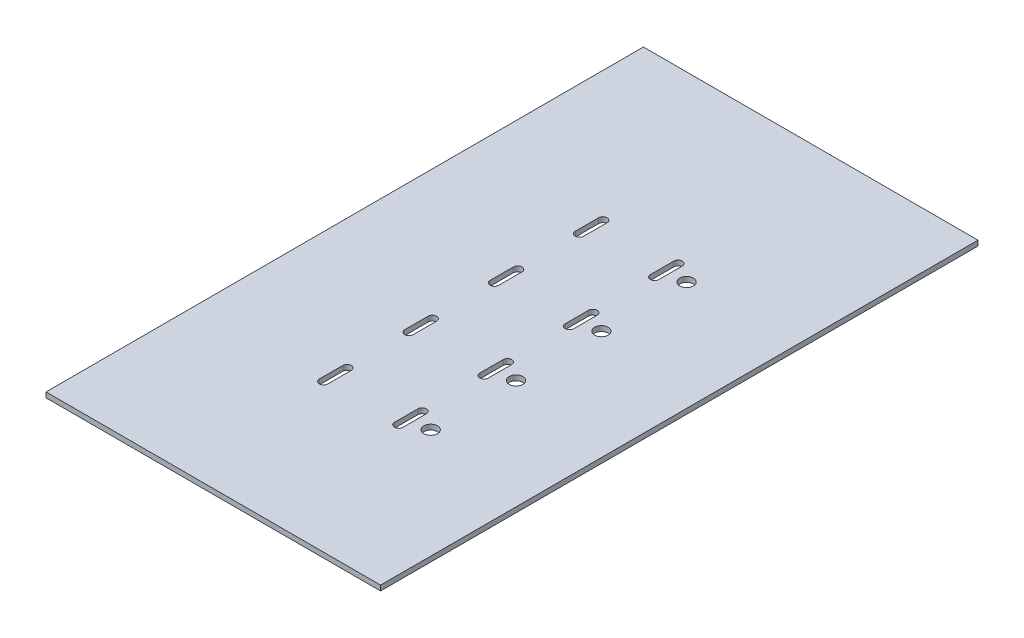
SolidWorks part; units mm, degrees
ref_plane "Front Plane" through (0, 0, 0) normal (0, 0, 1) x (1, 0, 0)
ref_plane "Top Plane" through (0, 0, 0) normal (0, 1, 0) x (1, 0, 0)
ref_plane "Right Plane" through (0, 0, 0) normal (1, 0, 0) x (0, 0, -1)
sketch "Sketch1" plane through (0, 0, 0) normal (0, 1, 0) x (1, 0, 0)
  line L1 (0, 0) -> (196, 0)
  line L2 (0, 0) -> (0, 350)
  line L3 (0, 350) -> (196, 350)
  line L4 (196, 0) -> (196, 350)
  dimension "D1" = 350
  dimension "D2" = 196
extrude "Boss-Extrude1" add sketch "Sketch1" along normal blind 3
hole_wizard "Ø8.0mm Dowel Hole1" positions "Sketch2" profile "Sketch3" hole size "Ø8.0" standard "AS" end condition up to next
sketch "Sketch2" plane through (0, 0, 0) normal (0, -1, 0) x (-1, 0, 0)
  point P0 (-131.875, 93.5)
  point P3 (-131.875, 143.5)
  point P6 (-131.875, 193.5067)
  point P9 (-131.875, 243.4059)
  point P13 (0, 0)
  point P14 (0, 0)
  point P15 (0, 0)
  point P16 (0, 0)
sketch "Sketch3" plane through (131.875, 0, -93.5) normal (1, 0, 0) x (0, 0, -1)
  line L0 (0, 0) -> (0, 3)
  line L1 (0, 3) -> (4, 3)
  line L2 (4, 3) -> (4, 0)
  line L5 (4, 0) -> (0, 0)
  line L11 (0, -6.35) -> (0, 107.95) construction
  dimension "Thru Hole Dia." = 8
  dimension "Thru Hole Depth" = 3
hole_wizard "Ø5.0mm Dowel Slot1" positions "Sketch4" profile "Sketch5" size "Ø5.0" standard "AS" slot yes end condition up to next
sketch "Sketch4" plane through (0, 0, 0) normal (0, -1, 0) x (-1, 0, 0)
  line L0 (-120, 84.15) -> (-120, 102.85) construction
  point P0 (-120, 93.5)
  point P7 (-76, 93.5)
  point P10 (-120, 143.5)
  point P13 (-76, 143.5)
  point P16 (-120, 193.5067)
  point P19 (-76, 193.5067)
  point P22 (-120, 243.4059)
  point P25 (-76, 243.4059)
  point P29 (0, 0)
  point P30 (0, 0)
  point P31 (0, 0)
  point P32 (0, 0)
  point P33 (0, 0)
  point P34 (0, 0)
  point P35 (0, 0)
  point P36 (0, 0)
  dimension "D1" = 18.7
sketch "Sketch5" plane through (120, 0, -93.5) normal (1, 0, 0) x (0, 0, -1)
  line L0 (0, 0) -> (0, 3)
  line L1 (0, 3) -> (2.5, 3)
  line L2 (2.5, 3) -> (2.5, 0)
  line L5 (2.5, 0) -> (0, 0)
  line L11 (0, -6.35) -> (0, 107.95) construction
  dimension "Thru Hole Dia." = 5
  dimension "Thru Hole Depth" = 3
